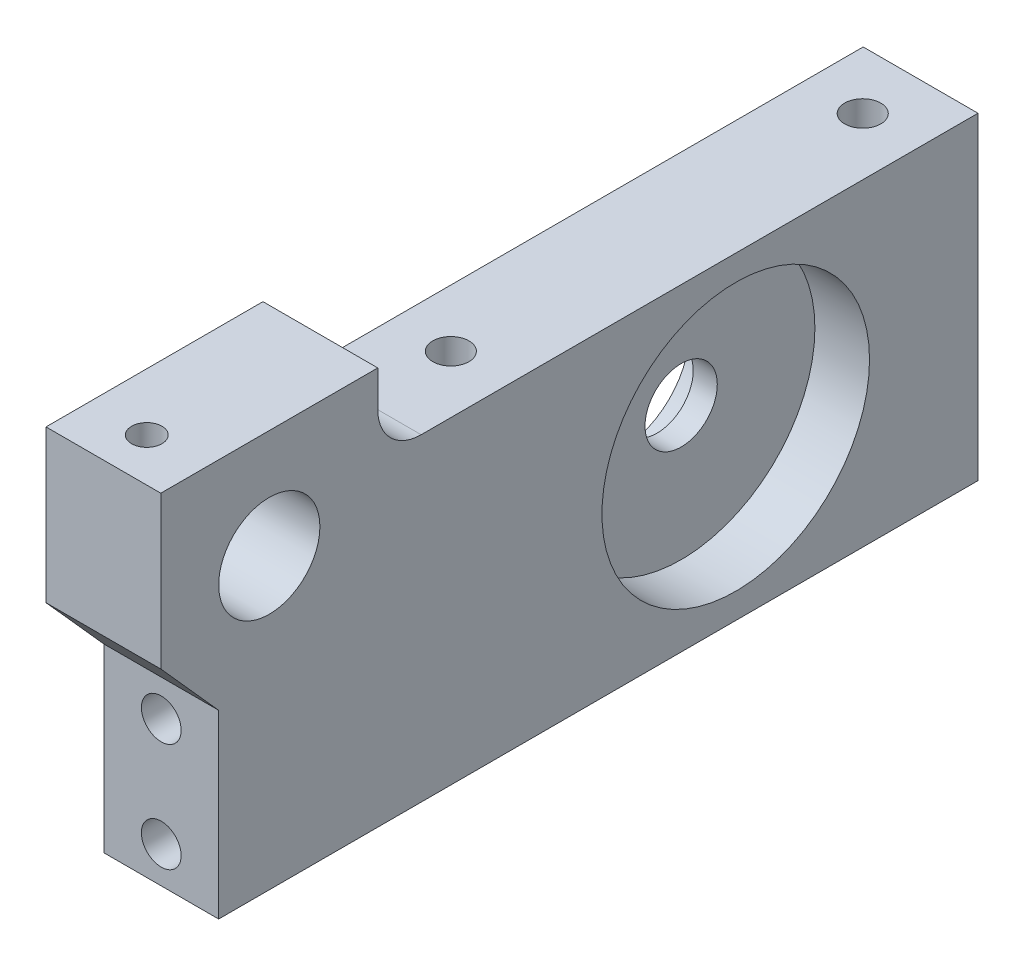
SolidWorks part; units mm, degrees
material "3.0205 (EN-AW 1200)"
ref_plane "Plano frontal" through (0, 0, 0) normal (0, 0, 1) x (1, 0, 0)
ref_plane "Plano superior" through (0, 0, 0) normal (0, 1, 0) x (1, 0, 0)
ref_plane "Plano direito" through (0, 0, 0) normal (1, 0, 0) x (0, 0, -1)
sketch "Esboço1" plane through (0, 0, 0) normal (1, 0, 0) x (0, 0, -1)
  line L0 (15, 15) -> (-15, 15)
  line L1 (-15, -6.0557) -> (-7, -15)
  line L2 (-15, 15) -> (-15, -6.0557)
  line L3 (-7, -40) -> (98, -40)
  line L5 (15, 4) -> (98, 4)
  line L7 (-7, -15) -> (-7, -40)
  line L10 (98, -40) -> (98, 4)
  line L14 (15, 4) -> (15, 15)
  circle A2 centre (0, 0) radius 7
  dimension "D3" = 14
  dimension "D4" = 40
  dimension "D5" = 15
  dimension "D1" = 44
  dimension "D2" = 15
  dimension "D6" = 12
  dimension "D7" = 15
  dimension "D12" = 105
  dimension "D14" = 25
  dimension "D15" = 7
extrude "Ressalto-extrusão1" add sketch "Esboço1" along normal mid plane 15.875 contours L2 L3 | L2 L3 region at (0, -16.3734, -42.5422)
hole_wizard "Escareado para parafuso de máquina com cabeça chata de M51" positions "Esboço10" profile "Esboço11" countersink size "M5" standard "Ansi Metric"
sketch "Esboço10" plane through (-33.0625, -33.7517, 15.0704) normal (0, 0, 1) x (1, 0, 0)
  line L0 (0, 0) -> (0, 16.8759) construction
  line L4 (-33.0625, 27.6959) -> (-33.0625, 13.7517) construction
  line L7 (-33.0625, 13.7517) -> (-33.0625, -1.2483) construction
  point P0 (-33.0625, 13.7517)
  point P2 (-33.0625, -1.2483)
  point P29 (33.0625, -1.2483)
  point P30 (33.0625, 13.7517)
sketch "Esboço11" plane through (-66.125, -20, 15.0704) normal (1, 0, 0) x (0, -1, 0)
  line L0 (0, 0) -> (0, 31.6524)
  line L1 (0, 31.6524) -> (2.75, 30)
  line L2 (2.75, 30) -> (2.75, 2.45)
  line L3 (2.75, 2.45) -> (5.2, 0)
  line L4 (5.2, 0) -> (0, 0)
  line L5 (-2.75, 2.45) -> (-5.2, 0) construction
  line L6 (0, 31.6524) -> (-2.75, 30) construction
  line L7 (0, -6.35) -> (0, 107.95) construction
  dimension "Hole Dia." = 5.5
  dimension "Hole Depth" = 30
  dimension "Near C'Sink Dia." = 10.4
  dimension "Near C'Sink Angle" = 90
  dimension "Drill Angle" = 118
hole_wizard "Escareado para parafuso de máquina com cabeça chata de M53" positions "Esboço14" profile "Esboço15" countersink size "M6" standard "Ansi Metric"
sketch "Esboço14" plane through (-33.0625, -47, -36.4602) normal (0, -1, 0) x (-1, 0, 0)
  line L0 (-41, 61.5398) -> (-25.125, 61.5398) construction
  point P0 (33.06, 49.5865)
  point P2 (33.06, -3.4135)
  point P4 (-33.06, -3.4135)
  point P6 (-33.06, 53.5398)
  dimension "D1" = 8
sketch "Esboço15" plane through (-66.1225, -47, -86.0467) normal (1, 0, 0) x (0, 0, -1)
  line L0 (0, 0) -> (0, 31.9828)
  line L1 (0, 31.9828) -> (3.3, 30)
  line L2 (3.3, 30) -> (3.3, 3)
  line L3 (3.3, 3) -> (6.3, 0)
  line L4 (6.3, 0) -> (0, 0)
  line L5 (-3.3, 3) -> (-6.3, 0) construction
  line L6 (0, 31.9828) -> (-3.3, 30) construction
  line L7 (0, -6.35) -> (0, 107.95) construction
  dimension "Hole Dia." = 6.6
  dimension "Hole Depth" = 30
  dimension "Near C'Sink Dia." = 12.6
  dimension "Near C'Sink Angle" = 90
  dimension "Drill Angle" = 118
hole_wizard "Broca de rosquear para tarraxa de M5x0.81" positions "Esboço16" profile "Esboço17" hole size "M5x0.8" standard "Ansi Metric"
sketch "Esboço16" plane through (-33.0625, 25, -36.4602) normal (0, 1, 0) x (1, 0, 0)
  line L0 (41, -45.4602) -> (25.12, -45.4602) construction
  line L3 (-41.005, -45.4602) -> (-25.125, -45.4602) construction
  point P9 (33.06, -45.4602)
  point P20 (-33.065, -45.4602)
sketch "Esboço17" plane through (-0.0025, 25, 9) normal (1, 0, 0) x (0, 0, 1)
  line L0 (0, 0) -> (0, 21.2618)
  line L1 (0, 21.2618) -> (2.1, 20)
  line L2 (2.1, 20) -> (2.1, 0)
  line L3 (2.1, 0) -> (0, 0)
  line L4 (0, 21.2618) -> (-2.1, 20) construction
  line L5 (0, -6.35) -> (0, 107.95) construction
  dimension "Hole Dia." = 4.2
  dimension "Hole Depth" = 20
  dimension "Drill Angle" = 118
hole_wizard "Broca de rosquear para tarraxa de M5x0.82" positions "Esboço18" profile "Esboço19" hole size "M5x0.8" standard "Ansi Metric"
sketch "Esboço18" plane through (-33.0625, -33.7517, -25) normal (0, 0, -1) x (-1, 0, 0)
  line L0 (-33.06, 37.7517) -> (-33.06, 43.7517) construction
  line L3 (33.065, 37.7517) -> (33.065, 43.7517) construction
  point P1 (-33.06, 43.7517)
  point P7 (33.065, 43.7517)
sketch "Esboço19" plane through (-0.0025, 10, -25) normal (1, 0, 0) x (0, 1, 0)
  line L0 (0, 0) -> (0, 21.2618)
  line L1 (0, 21.2618) -> (2.1, 20)
  line L2 (2.1, 20) -> (2.1, 0)
  line L3 (2.1, 0) -> (0, 0)
  line L4 (0, 21.2618) -> (-2.1, 20) construction
  line L5 (0, -6.35) -> (0, 107.95) construction
  dimension "Hole Dia." = 4.2
  dimension "Hole Depth" = 20
  dimension "Drill Angle" = 118
hole_wizard "Broca de rosquear para tarraxa de M6x1.01" positions "Esboço20" profile "Esboço21" hole size "M6x1.0" standard "Ansi Metric"
sketch "Esboço20" plane through (-33.0625, 4, -36.4602) normal (0, 1, 0) x (1, 0, 0)
  line L0 (41, 61.5398) -> (25.125, 61.5398) construction
  point P0 (33.06, 53.5398)
  point P3 (-33.06, 49.5398)
  point P14 (-33.06, -3.4135)
  point P17 (33.06, -3.4135)
  dimension "D1" = 8
sketch "Esboço21" plane through (-0.0025, 4, -90) normal (1, 0, 0) x (0, 0, 1)
  line L0 (0, 0) -> (0, 16.5022)
  line L1 (0, 16.5022) -> (2.5, 15)
  line L2 (2.5, 15) -> (2.5, 0)
  line L3 (2.5, 0) -> (0, 0)
  line L4 (0, 16.5022) -> (-2.5, 15) construction
  line L5 (0, -6.35) -> (0, 107.95) construction
  dimension "Hole Dia." = 5
  dimension "Hole Depth" = 15
  dimension "Drill Angle" = 118
hole_wizard "Escareado para SFHCS M51" positions "Esboço22" profile "Esboço23" countersink size "M5" standard "Ansi Metric"
sketch "Esboço22" plane through (-33.0625, -57, -36.4602) normal (0, -1, 0) x (-1, 0, 0)
  line L5 (-33.065, -14.4602) -> (-33.065, -26.4602) construction
  line L6 (-33.065, -26.4602) -> (-33.065, -46.4602) construction
  line L8 (33.065, -46.4602) -> (33.065, -26.4602) construction
  line L10 (33.065, -26.4602) -> (33.065, -14.4602) construction
  point P12 (-33.065, -14.4602)
  point P22 (-33.065, -26.4602)
  point P38 (33.065, -26.4602)
  point P41 (33.065, -14.4602)
sketch "Esboço23" plane through (0.0025, -57, -22) normal (1, 0, 0) x (0, 0, -1)
  line L0 (0, 0) -> (0, 31.6524)
  line L1 (0, 31.6524) -> (2.75, 30)
  line L2 (2.75, 30) -> (2.75, 3.35)
  line L3 (2.75, 3.35) -> (5.6, 0.5)
  line L4 (5.6, 0.5) -> (5.6, 0)
  line L5 (5.6, 0) -> (0, 0)
  line L6 (-2.75, 3.35) -> (-5.6, 0.5) construction
  line L7 (0, 31.6524) -> (-2.75, 30) construction
  line L8 (0, -6.35) -> (0, 107.95) construction
  dimension "Hole Dia." = 5.5
  dimension "Hole Depth" = 30
  dimension "C'Sink Dia." = 11.2
  dimension "C'Sink Angle" = 90
  dimension "Drill Angle" = 118
  dimension "Head Clearance" = 0.5
sketch "Sketch1" plane through (7.9375, 0, 0) normal (1, 0, 0) x (0, 0, -1)
  line L0 (64.5, 4) -> (64.5, -40) construction
  line L1 (15, 4) -> (98, 4) construction
  line L2 (-7, -40) -> (98, -40) construction
  line L3 (98, -40) -> (98, 4) construction
  circle A0 centre (64.5, -18) radius 18.5
  point P11 (83, -18)
  point P12 (98, -18)
  dimension "D1" = 37
  dimension "D2" = 15
extrude "Cut-Extrude1" cut sketch "Sketch1" against normal blind 7.55 contours A0
sketch "Sketch2" plane through (0.3875, 0, 0) normal (1, 0, 0) x (0, 0, -1)
  circle A0 centre (64.5, -18) radius 5
  dimension "D1" = 10
extrude "Cut-Extrude2" cut sketch "Sketch2" against normal through all
sketch "Sketch3" plane through (-7.9375, 0, 0) normal (-1, 0, 0) x (0, 0, 1)
  circle A0 centre (-64.5, -18) radius 9.5
  dimension "D1" = 19
extrude "Cut-Extrude3" cut sketch "Sketch3" against normal blind 5
fillet "Fillet1" radius 6 1 edges at (0, 4, -15)
